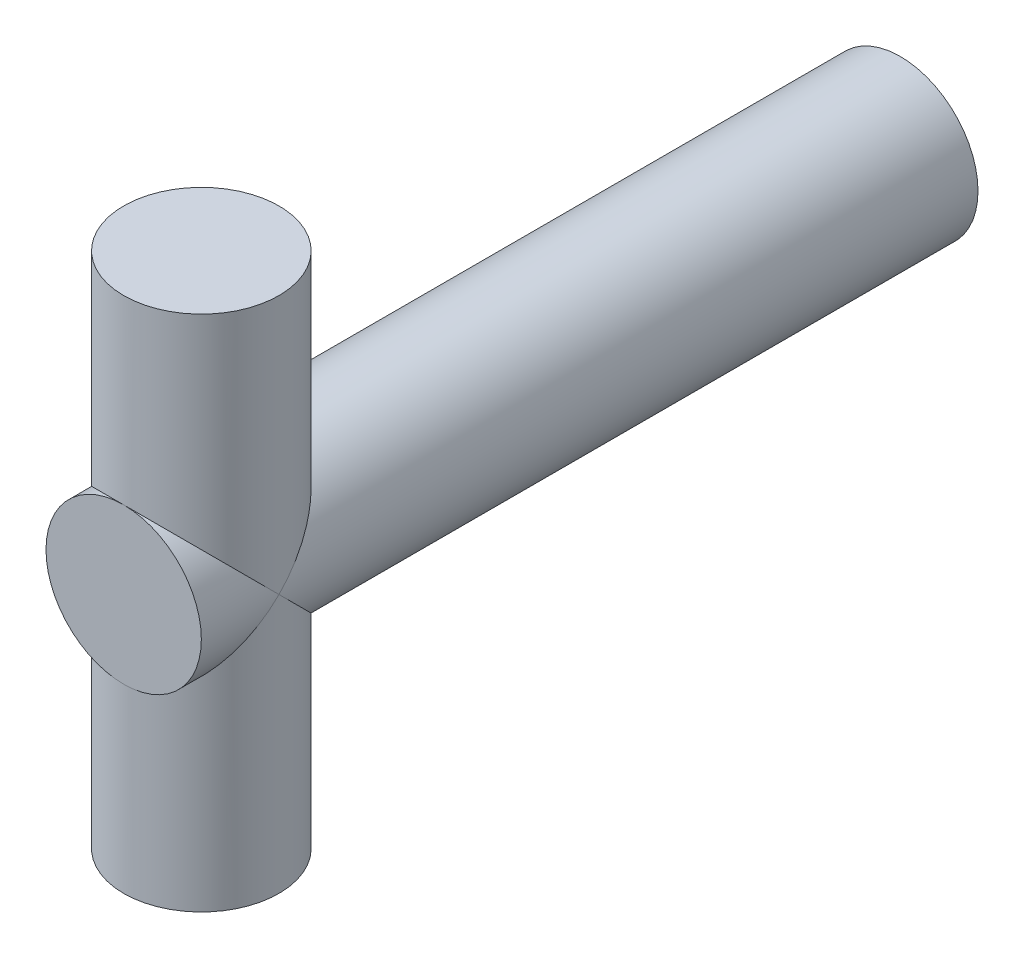
SolidWorks part; units mm, degrees
ref_plane "Front Plane" through (0, 0, 0) normal (0, 0, 1) x (1, 0, 0)
ref_plane "Top Plane" through (0, 0, 0) normal (0, 1, 0) x (1, 0, 0)
ref_plane "Right Plane" through (0, 0, 0) normal (1, 0, 0) x (0, 0, -1)
sketch "Sketch1" plane through (0, 0, 0) normal (0, 0, 1) x (1, 0, 0)
  circle A0 centre (0, 0) radius 1.5
  dimension "D1" = 3
extrude "Boss-Extrude1" add sketch "Sketch1" along normal blind 15
sketch "Sketch2" plane through (0, 0, 0) normal (0, 1, 0) x (1, 0, 0)
  line L0 (-1.5, -15) -> (1.5, -15) construction
  circle A0 centre (0, -13.5) radius 1.5
  dimension "D1" = 3
extrude "Boss-Extrude2" add sketch "Sketch2" along normal blind 5 and the other way blind 5
